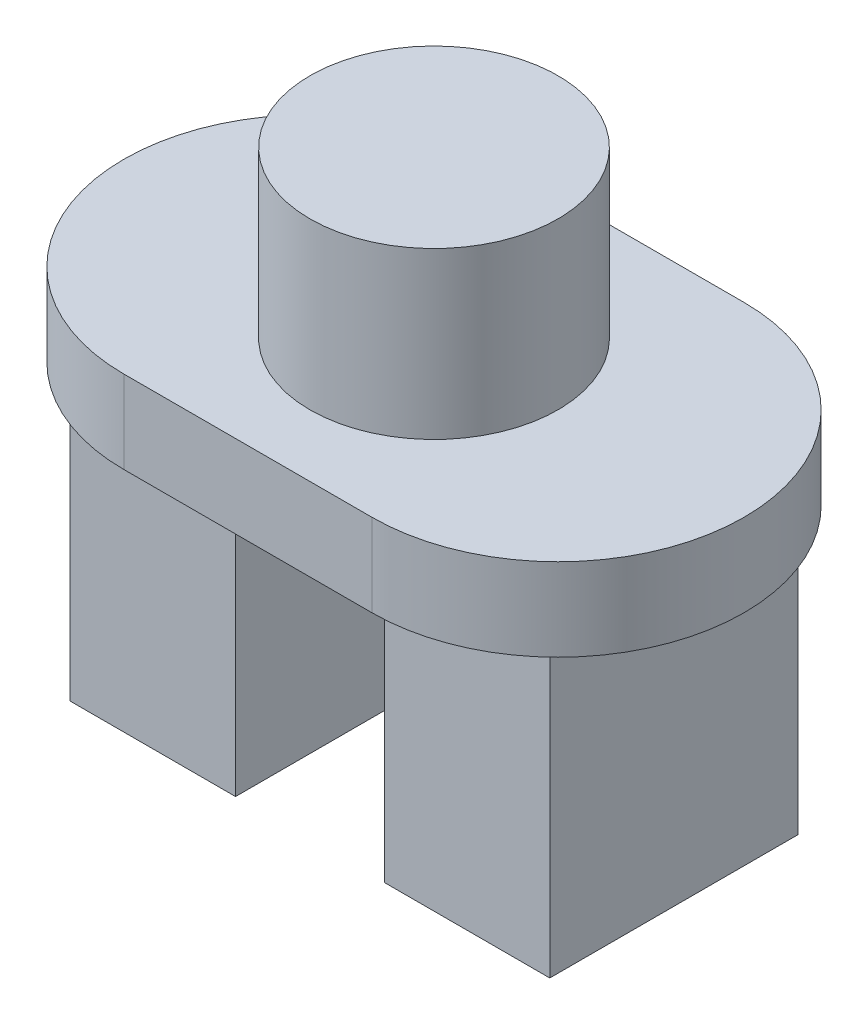
SolidWorks part; units mm, degrees
ref_plane "前视基准面" through (0, 0, 0) normal (0, 0, 1) x (1, 0, 0)
ref_plane "上视基准面" through (0, 0, 0) normal (0, 1, 0) x (1, 0, 0)
ref_plane "右视基准面" through (0, 0, 0) normal (1, 0, 0) x (0, 0, -1)
sketch "4段滑动开关草图" plane through (0, 0, 0) normal (0, 1, 0) x (1, 0, 0)
  line L0 (0.9, 0.0061) -> (-0.9, 0)
  line L1 (-1.5, -2.25) -> (1.5, -2.25)
  line L3 (-1.5, 2.25) -> (1.5, 2.25)
  line L5 (-0.9, 0) -> (-0.9, 1.5)
  line L6 (-0.9, 0) -> (-0.9, -1.5)
  line L7 (-0.9, 1.5) -> (-2.9, 1.5)
  line L8 (-0.9, -1.5) -> (-2.9, -1.5)
  line L9 (-2.9, 1.5) -> (-2.9, -1.5)
  line L10 (0, 2.25) -> (0, -2.25)
  line L11 (0.9, 0.0061) -> (0.9, 1.5)
  line L12 (0.9, 0.0061) -> (0.9, -1.5)
  line L13 (0.9, 1.5) -> (2.9, 1.5)
  line L14 (0.9, -1.5) -> (2.9, -1.5)
  line L15 (2.9, 1.5) -> (2.9, -1.5)
  circle A0 centre (0, 0) radius 1.5
  arc A1 (-1.5, 2.25) -> (-1.5, -2.25) centre (-1.5, 0) ccw
  arc A2 (1.5, 2.25) -> (1.5, -2.25) centre (1.5, 0) cw
  point P0 (0, 0)
extrude "凸台-拉伸1" add sketch "4段滑动开关草图" along normal blind 1 contours L1 A2 L3 A1
extrude "凸台-拉伸2" add sketch "4段滑动开关草图<4>" along normal blind 3 contours A0
sketch "4段滑动开关草图<4>" plane through (0, 0, 0) normal (0, 1, 0) x (1, 0, 0) same geometry as "4段滑动开关草图"
extrude "凸台-拉伸3" add sketch "4段滑动开关草图<5>" against normal blind 3.5 contours L9 L8 L6 L5 L7 | L15 L14 L12 L11 L13
sketch "4段滑动开关草图<5>" plane through (0, 0, 0) normal (0, 1, 0) x (1, 0, 0) same geometry as "4段滑动开关草图"
